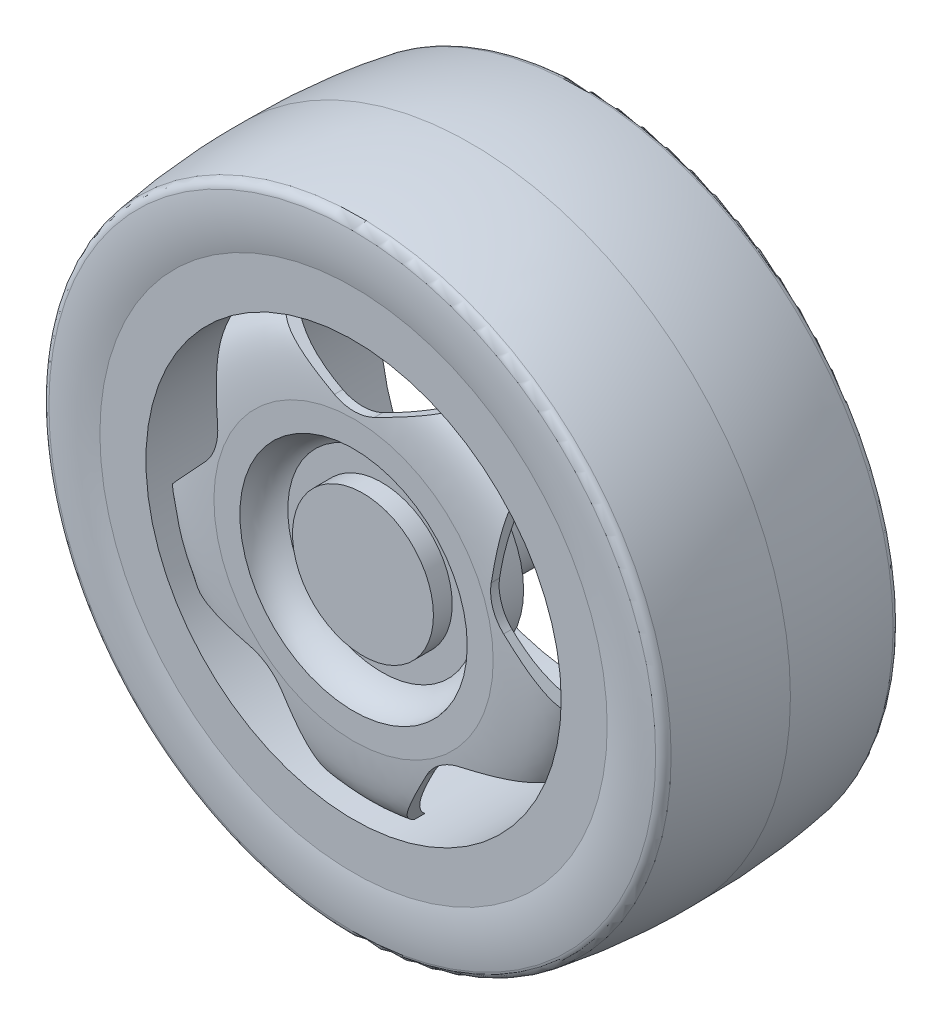
SolidWorks part; units mm, degrees
ref_plane "Front Plane" through (0, 0, 0) normal (0, 0, 1) x (1, 0, 0)
ref_plane "Top Plane" through (0, 0, 0) normal (0, 1, 0) x (1, 0, 0)
ref_plane "Right Plane" through (0, 0, 0) normal (1, 0, 0) x (0, 0, -1)
sketch "Sketch1" plane through (0, 0, 0) normal (1, 0, 0) x (0, 0, -1)
  line L0 (-0.0107, 12.1) -> (-0.0107, 14.8643)
  line L1 (-0.0107, 25.1) -> (24.9893, 25.1)
  line L2 (-0.0107, 22.1) -> (2.9893, 22.1)
  line L3 (2.9893, 10) -> (2.9893, 7.5)
  line L4 (2.9893, 7.5) -> (0.9893, 7.5)
  line L5 (0.9893, 7.5) -> (0.9893, 0)
  line L6 (-13.2759, 0) -> (14.215, 0) construction
  line L7 (-0.0107, 22.1) -> (-0.0107, 25.1)
  line L8 (24.9893, 25.1) -> (24.9893, 22.1)
  line L9 (24.9893, 22.1) -> (4.0868, 22.1)
  line L10 (0.9893, 14.8643) -> (0.9893, 12.992)
  line L11 (4.0868, 10) -> (8.0868, 10)
  line L12 (8.0868, 10) -> (8.0868, 0)
  line L13 (8.0868, 0) -> (0.9893, 0)
  arc A0 (-0.0107, 12.1) -> (2.9893, 10) centre (-0.3983, 8.3534) cw
  arc A1 (4.0868, 22.1) -> (0.9893, 14.8643) centre (9.2266, 15.6189) ccw
  arc A2 (0.9893, 12.992) -> (4.0868, 10) centre (-0.1123, 8.7522) cw
  spline S0 degree 3 poles (2.9893, 22.1) (1.2339, 21.0874) (0.2751, 20.019) (-0.0107, 14.8643) knots 0 0 0 0 1 1 1 1
  point P6 (3, 12)
  dimension "D5" = 2.2559
  dimension "D2" = 25
  dimension "D3" = 3
  dimension "D4" = 3
  dimension "D6" = 2
  dimension "D7" = 2.5
  dimension "D8" = 2
  dimension "D9" = 13
  dimension "D10" = 1
  dimension "D11" = 1
  dimension "D12" = 4
revolve "Revolve1" add sketch "Sketch1" angle 360 about L6
sketch "Sketch2" plane through (0, 0, 0.0107) normal (0, 0, 1) x (1, 0, 0)
  line L0 (0, 22.1) -> (0, 0) construction
  line L1 (-10, 19.7081) -> (-2.1298, 16.0027)
  line L2 (2.1298, 16.0027) -> (10, 19.7081)
  line L3 (15.6534, 15.6007) -> (14.5614, 6.9707)
  line L4 (15.8777, 2.9195) -> (21.8337, -3.4204)
  line L5 (19.6743, -10.0664) -> (11.1292, -11.6946)
  line L6 (7.6831, -14.1984) -> (3.494, -21.8221)
  line L7 (-3.494, -21.8221) -> (-7.6831, -14.1984)
  line L8 (-11.1292, -11.6946) -> (-19.6743, -10.0664)
  line L9 (-21.8337, -3.4204) -> (-15.8777, 2.9195)
  line L10 (-14.5614, 6.9707) -> (-15.6534, 15.6007)
  circle A0 centre (0, 0) radius 22.1 construction
  circle A1 centre (0, 0) radius 22.1 construction
  arc A2 (-2.1298, 16.0027) -> (2.1298, 16.0027) centre (0, 20.5264) ccw
  arc A3 (10, 19.7081) -> (-10, 19.7081) centre (0, 0) ccw
  arc A4 (14.5614, 6.9707) -> (15.8777, 2.9195) centre (19.5218, 6.343) ccw
  arc A5 (21.8337, -3.4204) -> (15.6534, 15.6007) centre (0, 0) ccw
  arc A6 (11.1292, -11.6946) -> (7.6831, -14.1984) centre (12.0651, -16.6062) ccw
  arc A7 (3.494, -21.8221) -> (19.6743, -10.0664) centre (0, 0) ccw
  arc A8 (-7.6831, -14.1984) -> (-11.1292, -11.6946) centre (-12.0651, -16.6062) ccw
  arc A9 (-19.6743, -10.0664) -> (-3.494, -21.8221) centre (0, 0) ccw
  arc A10 (-15.8777, 2.9195) -> (-14.5614, 6.9707) centre (-19.5218, 6.343) ccw
  arc A11 (-15.6534, 15.6007) -> (-21.8337, -3.4204) centre (0, 0) ccw
  point P12 (0, 15)
  point P35 (0, 0)
  dimension "D3" = 5
  dimension "D1" = 10
  dimension "D2" = 15
  dimension "D4" = 5
extrude "Cut-Extrude1" cut sketch "Sketch2" against normal blind 10
sketch "Sketch3" plane through (0, 0, -8.0868) normal (0, 0, -1) x (-1, 0, 0)
  circle A0 centre (0, 0) radius 6
  dimension "D1" = 12
extrude "Boss-Extrude1" add sketch "Sketch3" along normal blind 25
sketch "Sketch4" plane through (0, 0, -33.0868) normal (0, 0, -1) x (-1, 0, 0)
  line L0 (-2.5475, 2.4) -> (2.5475, 2.4)
  line L1 (-3.5, 0) -> (3.5, 0) construction
  line L2 (-2.5475, -2.4) -> (2.5475, -2.4)
  arc A0 (-2.5475, 2.4) -> (-2.5475, -2.4) centre (0, 0) ccw
  arc A1 (2.5475, -2.4) -> (2.5475, 2.4) centre (0, 0) ccw
  dimension "D1" = 7
  dimension "D2" = 2.4
extrude "Cut-Extrude2" cut sketch "Sketch4" against normal blind 12
sketch "Sketch5" plane through (0, 0, 0) normal (1, 0, 0) x (0, 0, -1)
  line L1 (-0.0107, 25.1) -> (-0.0107, -25.1) construction
  line L2 (24.9893, -25.1) -> (24.9893, 25.1) construction
  line L3 (12.4893, 34) -> (12.4893, 27) construction
  line L4 (0, 0) -> (33.0868, 0) construction
  line L5 (33.0868, -2.4) -> (33.0868, 2.4) construction
  line L6 (-0.0107, 27) -> (-0.0107, 24.9185)
  line L7 (-0.0107, 24.9185) -> (24.9893, 25.1)
  line L8 (24.9893, 25.1) -> (24.9893, 27)
  arc A0 (12.4893, 34) -> (0.6779, 33.1166) centre (11.5988, -33.4941) ccw
  arc A1 (-0.1468, 32.2936) -> (-0.0107, 27) centre (13.6641, 30) ccw
  arc A2 (-0.1468, 32.2936) -> (0.6779, 33.1166) centre (0.8397, 32.1297) cw
  arc A3 (25.1253, 32.2936) -> (24.9893, 27) centre (11.3145, 30) cw
  arc A4 (25.1253, 32.2936) -> (24.3006, 33.1166) centre (24.1389, 32.1297) ccw
  arc A5 (12.4893, 34) -> (24.3006, 33.1166) centre (13.3798, -33.4941) cw
  point P6 (12.4893, 34)
  point P7 (-0.0107, 33)
  point P8 (12.4893, 31.1)
  point P21 (-0.0107, 33)
  dimension "D3" = 67.5
  dimension "D4" = 14
  dimension "D5" = 1
  dimension "D2" = 6
  dimension "D6" = 34
revolve "Revolve2" add sketch "Sketch5" angle 360 about L4
